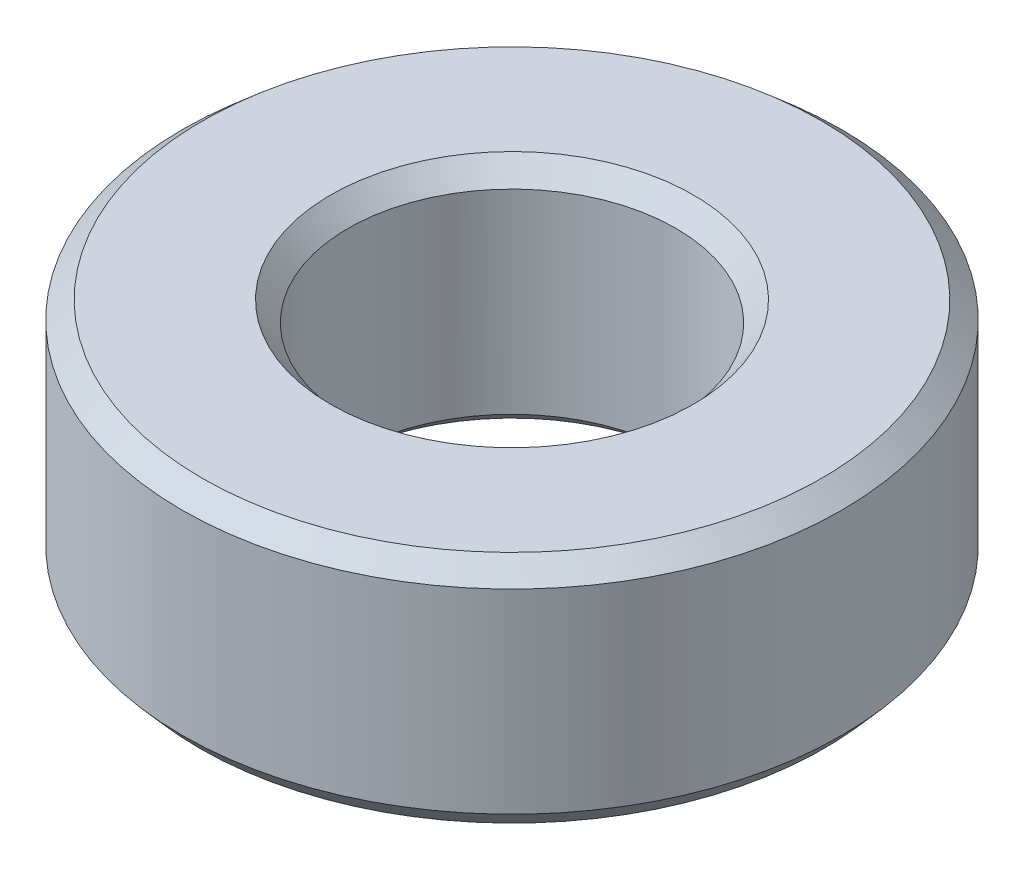
SolidWorks part; units mm, degrees
ref_plane "Front Plane" through (0, 0, 0) normal (0, 0, 1) x (1, 0, 0)
ref_plane "Top Plane" through (0, 0, 0) normal (0, 1, 0) x (1, 0, 0)
ref_plane "Right Plane" through (0, 0, 0) normal (1, 0, 0) x (0, 0, -1)
sketch "Sketch1" plane through (0, 0, 0) normal (0, 1, 0) x (1, 0, 0)
  circle A0 centre (0, 0) radius 27.5
  dimension "SLEEVE_OD" = 55
extrude "Boss-Extrude1" add sketch "Sketch1" along normal blind 19.4047
sketch "Sketch2" plane through (0, 0, 0) normal (0, 1, 0) x (1, 0, 0)
  circle A0 centre (0, 0) radius 13.6661
  dimension "BORE_D" = 27.3321
extrude "Cut-Extrude1" cut sketch "Sketch2" along normal through all
chamfer "Chamfer1" distance 1.464 angle 48.88 4 edges at (0, 19.4047, 13.6661) (0, 0, 13.6661) (0, 0, 27.5) (0, 19.4047, 27.5) first distance on face at (0, 19.4047, 13.6661) first distance on face at (0, 0, 13.6661) first distance on face at (0, 19.4047, 27.5)
